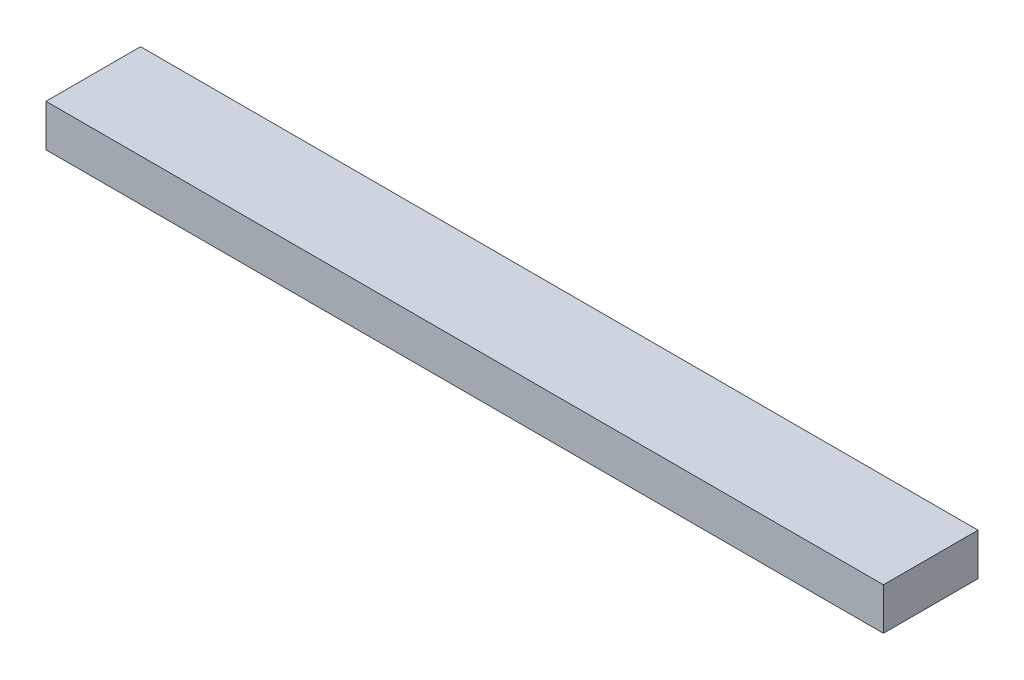
SolidWorks part; units mm, degrees
material "MDF"
ref_plane "Front Plane" through (0, 0, 0) normal (0, 0, 1) x (1, 0, 0)
ref_plane "Top Plane" through (0, 0, 0) normal (0, 1, 0) x (1, 0, 0)
ref_plane "Right Plane" through (0, 0, 0) normal (1, 0, 0) x (0, 0, -1)
sketch "Sketch1" plane through (0, 0, 0) normal (0, 0, 1) x (1, 0, 0)
  line L0 (0, -297.4265) -> (0, 297.4265) construction
  line L1 (-126.4888, -311.15) -> (126.4888, -311.15)
  line L2 (-126.4888, -311.15) -> (-126.4888, -298.45)
  line L3 (-126.4888, -298.45) -> (126.4888, -298.45)
  line L4 (0, -311.15) -> (0, -298.45) construction
  line L5 (126.4888, -311.15) -> (126.4888, -298.45)
  dimension "D1" = 12.7
extrude "Boss-Extrude1" add sketch "Sketch1" along normal up to surface (28.575 mm away)
hole_wizard "Hole1" positions "Sketch2" profile "Sketch3" legacy
sketch "Sketch2" plane through (0, 0, -25.4) normal (0, 0, -1) x (-1, 0, 0)
  line L0 (218.5638, 0) -> (218.5638, -437.642) construction
  line L4 (104.2638, 0) -> (104.2638, -298.45) construction
  line L13 (120.1388, -460.375) -> (120.1388, -311.15) construction
  line L16 (126.4888, -311.15) -> (113.7888, -311.15) construction
  line L18 (126.4888, -304.8) -> (-126.4888, -304.8) construction
  line L22 (94.7388, -276.225) -> (-94.7388, -276.225) construction
  line L24 (-94.7388, -285.75) -> (-94.7388, -266.7) construction
  line L26 (94.7388, -285.75) -> (94.7388, -266.7) construction
  line L27 (-94.7388, 0) -> (-94.7388, -19.05) construction
  line L29 (94.7388, 0) -> (94.7388, -19.05) construction
  line L31 (94.7388, -9.525) -> (-94.7388, -9.525) construction
  point P15 (218.5638, -31.75)
  point P17 (218.5638, -218.821)
  point P19 (218.5638, -418.592)
  point P28 (104.2638, -19.05)
  point P30 (104.2638, -149.225)
  point P32 (104.2638, -279.4)
  point P69 (120.1388, -330.2)
  point P71 (120.1388, -441.325)
  point P76 (-120.1388, -441.325)
  point P77 (-120.1388, -330.2)
  point P80 (-104.2638, -279.4)
  point P81 (-104.2638, -149.225)
  point P82 (-104.2638, -19.05)
  point P83 (-218.5638, -418.592)
  point P84 (-218.5638, -218.821)
  point P85 (-218.5638, -31.75)
  point P99 (0, -304.8)
  point P101 (107.4388, -304.8)
  point P103 (-107.4388, -304.8)
  point P127 (75.6888, -276.225)
  point P129 (0, -276.225)
  point P131 (-75.6888, -276.225)
  point P152 (75.6888, -9.525)
  point P154 (0, -9.525)
  point P156 (-75.6888, -9.525)
  point P158 (0, 0)
sketch "Sketch3" plane through (75.6888, -9.525, -25.4) normal (1, 0, 0) x (0, 1, 0)
  line L0 (0, 0) -> (0, 39.0539)
  line L1 (0, 39.0539) -> (1.5875, 38.1)
  line L2 (1.5875, 38.1) -> (1.5875, 4.0177)
  line L3 (1.5875, 4.0177) -> (5.08, 0)
  line L4 (5.08, 0) -> (0, 0)
  line L5 (0, -14.3089) -> (0, 102.4216) construction
  line L6 (0, 39.0539) -> (-1.5875, 38.1) construction
  line L7 (-1.5875, 4.0177) -> (-5.08, 0) construction
  dimension "Diameter" = 3.175
  dimension "Depth" = 38.1
  dimension "C-Sink Diameter" = 10.16
  dimension "C-Sink Angle" = 82
  dimension "Drill Angle" = 118
